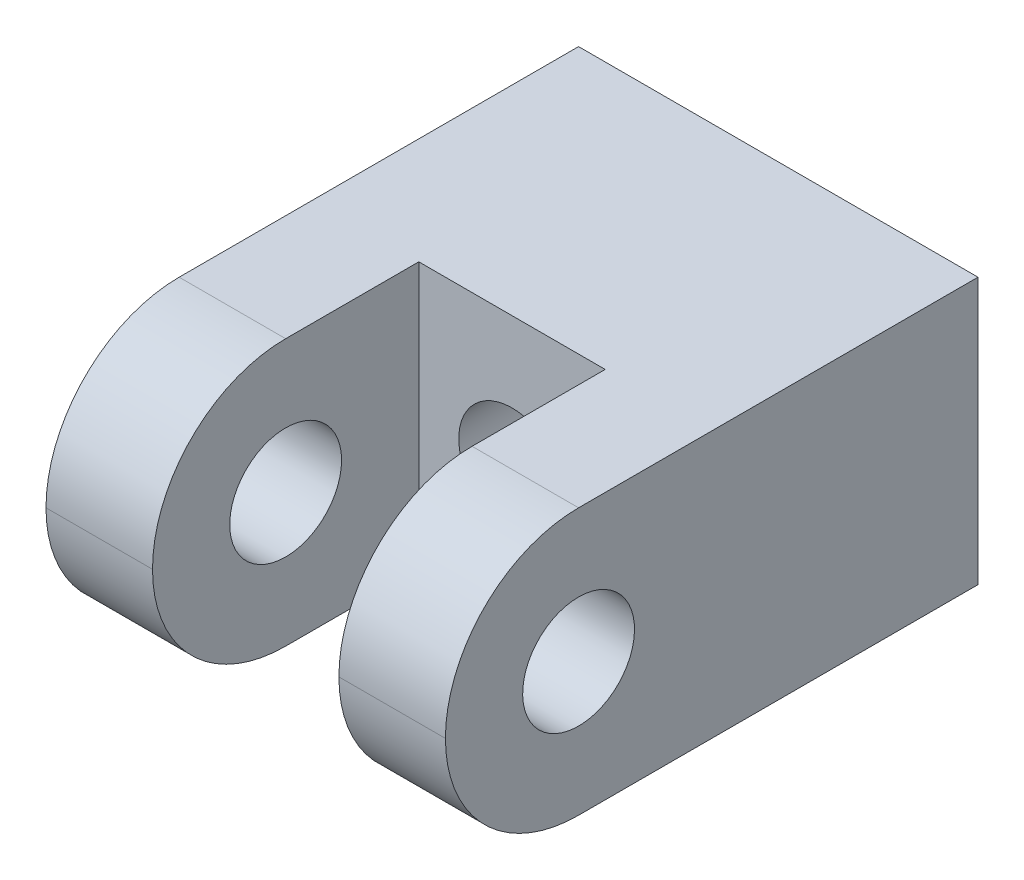
SolidWorks part; units mm, degrees
ref_plane "正面" through (0, 0, 0) normal (0, 0, 1) x (1, 0, 0)
ref_plane "平面" through (0, 0, 0) normal (0, 1, 0) x (1, 0, 0)
ref_plane "右側面" through (0, 0, 0) normal (1, 0, 0) x (0, 0, -1)
sketch "ｽｹｯﾁ1" plane through (0, 0, 0) normal (0, 0, 1) x (1, 0, 0)
  line L1 (-7.5, -5) -> (7.5, -5)
  line L2 (-7.5, -5) -> (-7.5, 5)
  line L3 (-7.5, 5) -> (7.5, 5)
  line L4 (7.5, -5) -> (7.5, 5)
  line L5 (-7.5, -5) -> (7.5, 5) construction
  line L6 (-7.5, 5) -> (7.5, -5) construction
  circle A0 centre (0, 0) radius 2
  point P0 (0, 0)
  dimension "D2" = 4
  dimension "D1" = 10
  dimension "D3" = 15
extrude "ﾎﾞｽ - 押し出し1" add sketch "ｽｹｯﾁ1" along normal blind 10
sketch "ｽｹｯﾁ2" plane through (0, 0, 10) normal (0, 0, 1) x (1, 0, 0)
  line L0 (-7.5, -5) -> (7.5, -5) construction
  line L1 (-7.5, 5) -> (-3.5, 5)
  line L2 (-7.5, 5) -> (-7.5, -5)
  line L3 (-7.5, -5) -> (-3.5, -5)
  line L4 (-3.5, 5) -> (-3.5, -5)
  line L5 (7.5, 5) -> (-7.5, 5) construction
  line L6 (3.5, 5) -> (7.5, 5)
  line L7 (3.5, 5) -> (3.5, -5)
  line L8 (3.5, -5) -> (7.5, -5)
  line L9 (7.5, 5) -> (7.5, -5)
  dimension "D1" = 4
  dimension "D2" = 4
extrude "ﾎﾞｽ - 押し出し2" add sketch "ｽｹｯﾁ2" along normal blind 10
sketch "ｽｹｯﾁ3" plane through (7.5, 0, 0) normal (1, 0, 0) x (0, 0, -1)
  line L0 (-20, -5) -> (-20, 5) construction
  circle A0 centre (-15, 0) radius 2.1
  dimension "D1" = 5
  dimension "D2" = 4.2
extrude "ｶｯﾄ - 押し出し1" cut sketch "ｽｹｯﾁ3" against normal blind 16
fillet "ﾌｨﾚｯﾄ1" radius 5 4 edges at (5.5, -5, 20) (5.5, 5, 20) (-5.5, 5, 20) (-5.5, -5, 20)
